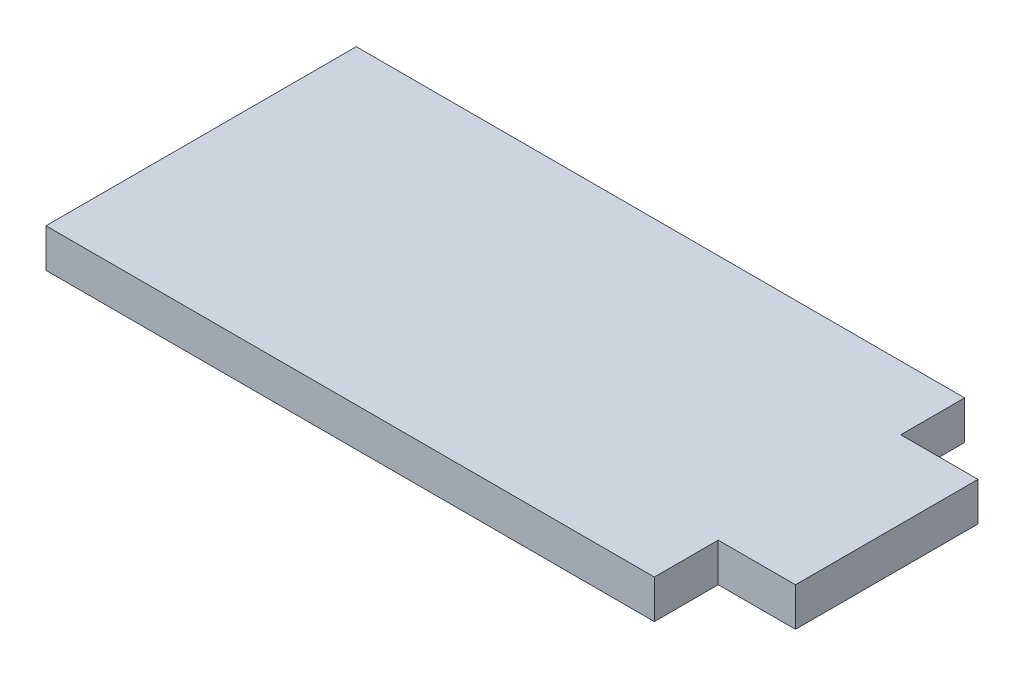
SolidWorks part; units mm, degrees
material "Cedar"
ref_plane "Front Plane" through (0, 0, 0) normal (0, 0, 1) x (1, 0, 0)
ref_plane "Top Plane" through (0, 0, 0) normal (0, 1, 0) x (1, 0, 0)
ref_plane "Right Plane" through (0, 0, 0) normal (1, 0, 0) x (0, 0, -1)
sketch "Sketch1" plane through (0, 0, 0) normal (0, 1, 0) x (1, 0, 0)
  line L0 (-25, 5.25) -> (25, 5.25)
  line L1 (25, 5.25) -> (25, 0)
  line L2 (25, 0) -> (31.35, 0)
  line L3 (31.35, 0) -> (31.35, -15)
  line L4 (31.35, -15) -> (25, -15)
  line L5 (25, -15) -> (25, -20.25)
  line L6 (25, -20.25) -> (-25, -20.25)
  line L7 (-25, -20.25) -> (-25, -15)
  line L8 (-25, -15) -> (-31.35, -15)
  line L9 (-31.35, -15) -> (-31.35, 0)
  line L10 (-31.35, 0) -> (-25, 0)
  line L11 (-25, 0) -> (-25, 5.25)
  line L12 (-25, 0) -> (-25, -15) construction
  point P11 (0, 5.25)
  point P14 (-31.35, -7.5)
  dimension "D1" = 6.35
  dimension "D2" = 15
  dimension "D3" = 50
  dimension "D4" = 25.5
extrude "Boss-Extrude1" add sketch "Sketch1" along normal blind 3.175 contours L11 L12 L7 L6 L5 L4 L3 L2 L1 L0 region at (1.9585, 0, 7.5)
equation "\"length\" = 25.5mm"
equation "\"w_mach\"= 50mm"
equation "\"w_tab\" = 15mm"
equation "\"t_wood\"= 0.125in"
equation "\"t_side\"= 0.25in"
equation "\"D1@Sketch1\"=\"t_side\""
equation "\"D2@Sketch1\"=\"w_tab\""
equation "\"D3@Sketch1\"=\"w_mach\""
equation "\"D4@Sketch1\"=\"length\""
equation "\"D1@Boss-Extrude1\"=\"t_wood\""
